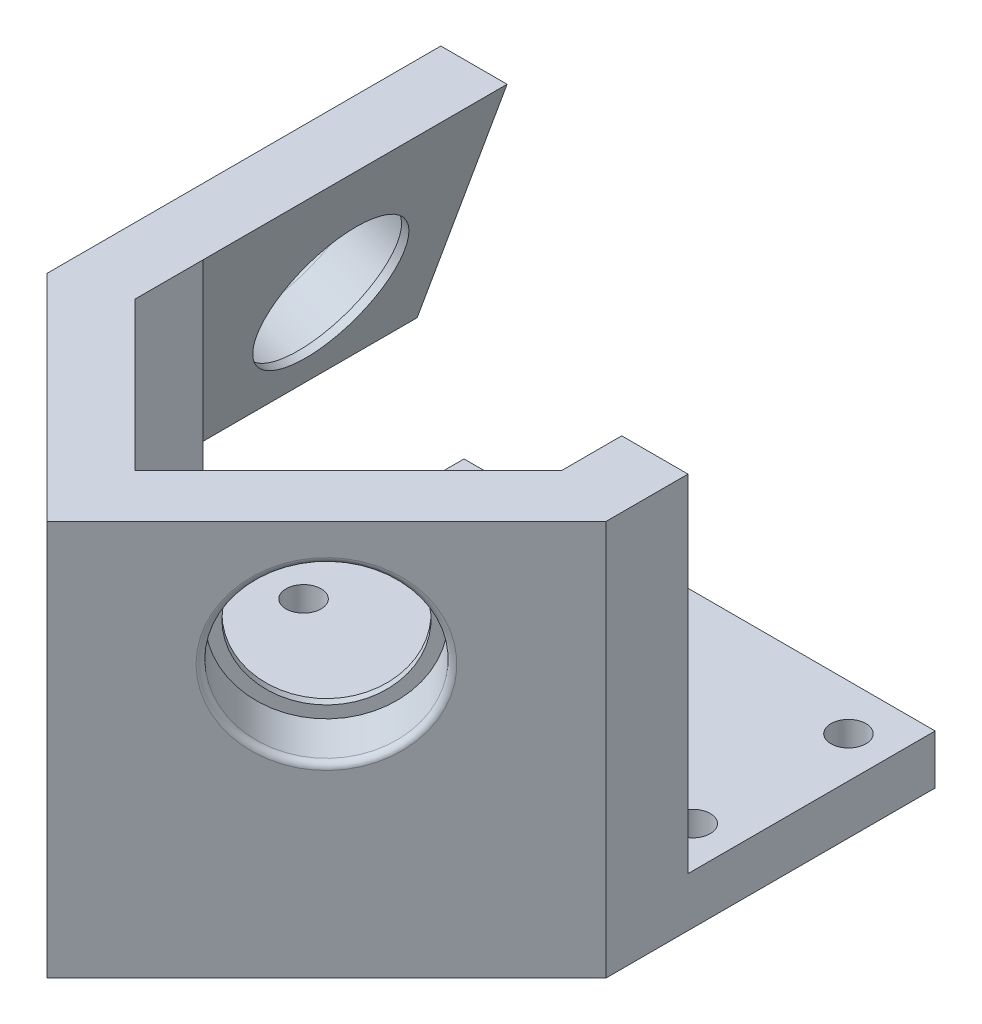
SolidWorks part; units mm, degrees
ref_plane "Front Plane" through (0, 0, 0) normal (0, 0, 1) x (1, 0, 0)
ref_plane "Top Plane" through (0, 0, 0) normal (0, 1, 0) x (1, 0, 0)
ref_plane "Right Plane" through (0, 0, 0) normal (1, 0, 0) x (0, 0, -1)
sketch "Sketch1" plane through (0, 0, 0) normal (0, 1, 0) x (1, 0, 0)
  line L0 (-35.921, 0) -> (0, 35.921)
  line L1 (-35.921, 0) -> (0, -35.921)
  line L2 (0, 35.921) -> (35.921, 0)
  line L3 (0, -35.921) -> (35.921, 0)
  line L4 (-35.921, 0) -> (35.921, 0) construction
  line L5 (0, 35.921) -> (0, -35.921) construction
  point P1 (0, 0)
  dimension "D1" = 50.8
  dimension "D2" = 50.8
extrude "Boss-Extrude1" add sketch "Sketch1" along normal mid plane 31.75
sketch "Sketch2" plane through (17.9605, 0, 17.9605) normal (0.7071, 0, 0.7071) x (0.7071, 0, -0.7071)
  circle A0 centre (0, 0) radius 11.05
  dimension "D1" = 22.1
extrude "Cut-Extrude1" cut sketch "Sketch2" against normal blind 8
sketch "Sketch3" plane through (-17.9605, 0, 17.9605) normal (-0.7071, 0, 0.7071) x (0.7071, 0, 0.7071)
  circle A0 centre (0, 0) radius 11.05
  dimension "D1" = 22.1
extrude "Cut-Extrude2" cut sketch "Sketch3" against normal blind 8
sketch "Sketch4" plane through (0, 15.875, 0) normal (0, 1, 0) x (1, 0, 0)
  line L0 (25.4, 10.521) -> (-25.4, 10.521)
  line L1 (35.921, 0) -> (0, 35.921) construction
  line L2 (0, 35.921) -> (-35.921, 0) construction
  line L3 (-25.4, 10.521) -> (0, 35.921)
  line L4 (0, 35.921) -> (25.4, 10.521)
  dimension "D1" = 25.4
extrude "Cut-Extrude3" cut sketch "Sketch4" against normal through all
sketch "Sketch5" plane through (0, 0, -10.521) normal (0, 0, -1) x (-1, 0, 0)
  line L0 (-35.921, 15.875) -> (-35.921, -15.875)
  line L1 (-35.921, -15.875) -> (39.135, -15.875)
  line L2 (39.135, -15.875) -> (27.579, 15.875)
  line L3 (27.579, 15.875) -> (-35.921, 15.875)
  line L4 (25.4, -15.875) -> (-25.4, -15.875) construction
  line L5 (-35.921, 15.875) -> (-35.921, -15.875) construction
  line L8 (25.4, 15.875) -> (-25.4, 15.875) construction
  point P6 (0, 0)
  dimension "D1" = 70
  dimension "D2" = 63.5
extrude "Boss-Extrude2" add sketch "Sketch5" against normal up to surface and the other way blind 31.75 up to face at (30.6605, 0, -5.2605)
sketch "Sketch6" plane through (-29.455, 10.7207, 0) normal (-0.9397, 0.342, 0) x (0, 0, 1)
  line L0 (-42.271, -28.3026) -> (-42.271, 5.4851) construction
  line L1 (-42.271, -28.3026) -> (-10.521, -28.3026) construction
  circle A0 centre (-26.396, -11.4088) radius 11.05
  point P4 (-42.271, -11.4088)
  point P7 (-26.396, -28.3026)
  dimension "D1" = 22.1
extrude "Cut-Extrude4" cut sketch "Sketch6" against normal through all
sketch "Sketch7" plane through (0, 0, -42.271) normal (0, 0, -1) x (-1, 0, 0)
  line L1 (-35.921, -15.875) -> (39.135, -15.875) construction
  line L3 (19.0656, 15.875) -> (30.6216, -15.875)
  line L4 (-35.921, -15.875) -> (30.6216, -15.875)
  line L5 (39.135, -15.875) -> (27.579, 15.875) construction
  line L6 (27.579, 15.875) -> (-35.921, 15.875) construction
  line L7 (-35.921, -15.875) -> (-35.921, 15.875)
  line L8 (-35.921, 15.875) -> (19.0656, 15.875)
  dimension "D3" = 8
extrude "Cut-Extrude5" cut sketch "Sketch7" against normal blind 31.75
sketch "Sketch8" plane through (0, 15.875, 0) normal (0, 1, 0) x (1, 0, 0)
  line L5 (-42.1413, -6.2203) -> (-8.2965, -39.8855)
  line L6 (0, -35.921) -> (0, -57.0039)
  line L13 (0, -57.0039) -> (-46.5861, -10.6651)
  line L14 (-46.5861, -10.6651) -> (-42.1413, -6.2203)
  line L15 (-8.2965, -39.8855) -> (-8.2965, -27.6245)
  line L16 (-35.921, 0) -> (0, -35.921) construction
  line L17 (-8.2965, -27.6245) -> (0, -35.921)
  line L18 (-25.4, 10.521) -> (-35.921, 0) construction
extrude "Boss-Extrude3" [suppressed] add sketch "Sketch8" against normal up to surface (25.4 mm away) up to face at (2.1042, -15.875, 2.9758)
sketch "Sketch9" plane through (0, -15.875, 0) normal (0, -1, 0) x (1, 0, 0)
  line L0 (-25.4, -10.521) -> (-35.921, 0)
  line L1 (-35.921, 0) -> (-46.442, -10.521)
  line L2 (-46.442, -10.521) -> (-25.4, -10.521)
  line L3 (-35.921, 0) -> (0, 35.921) construction
extrude "Boss-Extrude4" add sketch "Sketch9" against normal up to surface (31.75 mm away) up to face at (-9.1964, 15.875, -10.0783)
sketch "Sketch10" plane through (0, 0, -42.271) normal (0, 0, -1) x (-1, 0, 0)
  line L0 (39.135, -15.875) -> (27.579, 15.875) construction
  line L1 (39.135, -15.875) -> (27.579, 15.875)
  line L6 (27.579, 15.875) -> (39.135, -15.875)
  line L7 (39.135, -15.875) -> (46.442, -15.875)
  line L8 (46.442, -15.875) -> (46.442, 15.875)
  line L9 (46.442, 15.875) -> (27.579, 15.875)
  line L10 (27.579, 15.875) -> (39.135, -15.875)
  line L11 (39.135, -15.875) -> (46.442, -15.875)
  line L12 (46.442, -15.875) -> (46.442, 15.875)
  line L13 (46.442, 15.875) -> (27.579, 15.875)
  line M7 (39.135, -15.875) -> (27.579, 15.875)
  dimension "D1" = 0
extrude "Cut-Extrude6" cut sketch "Sketch10" against normal through all contours L12 L13 L11 M7 region at (-39.4743, 2.3367, -42.271)
sketch "Sketch11" plane through (0, -15.875, 0) normal (0, -1, 0) x (1, 0, 0)
  line L3 (-30.6216, -10.521) -> (-39.135, -10.521)
  line L4 (-39.135, -42.271) -> (-39.135, -3.214) construction
  line L5 (-39.135, -10.521) -> (-39.135, -3.214)
  line L10 (0, 35.921) -> (-39.135, -3.214)
  line L11 (-39.135, -3.214) -> (-39.135, -42.271)
  line L12 (-39.135, -42.271) -> (-30.6216, -42.271)
  line L13 (-30.6216, -42.271) -> (-30.6216, -10.521)
  line L21 (-30.6216, -10.521) -> (35.921, -10.521)
  line L22 (35.921, -10.521) -> (35.921, 0)
  line L23 (35.921, 0) -> (0, 35.921)
  line L24 (0, 35.921) -> (-39.135, -3.214)
  line L29 (-30.6216, -10.521) -> (35.921, -10.521)
  line L30 (35.921, -10.521) -> (35.921, 0)
  line L31 (35.921, 0) -> (0, 35.921)
  dimension "D1" = 0
extrude "Boss-Extrude5" add sketch "Sketch11" along normal blind 12.7
sketch "Sketch12" plane through (0, -28.575, 0) normal (0, -1, 0) x (1, 0, 0)
  line L0 (35.921, -10.521) -> (35.921, 0)
  line L1 (35.921, 0) -> (0, 35.921)
  line L2 (0, 35.921) -> (-39.135, -3.214)
  line L3 (-39.135, -3.214) -> (-39.135, -42.271)
  line L4 (-39.135, -42.271) -> (35.921, -42.271)
  line L5 (35.921, -42.271) -> (35.921, -10.521)
  point P10 (0, 0)
  point P13 (-36.8238, -0.9028)
extrude "Boss-Extrude6" add sketch "Sketch12" along normal blind 6.35
sketch "Sketch14" plane through (0, 0, -10.521) normal (0, 0, -1) x (-1, 0, 0)
  line L0 (35.244, -28.575) -> (19.0656, 15.875)
  line L1 (39.135, -34.925) -> (26.3581, -34.925)
  line L2 (19.0656, 15.875) -> (8.4238, 15.875)
  line L3 (24.6023, -28.575) -> (8.4238, 15.875)
  line L4 (19.0656, 15.875) -> (-35.921, 15.875) construction
  line L5 (30.6216, -15.875) -> (19.0656, 15.875) construction
  line L6 (39.135, -34.925) -> (-35.921, -34.925) construction
  line L7 (39.135, -34.925) -> (39.135, -28.575)
  line L8 (39.135, -28.575) -> (35.244, -28.575)
  line L9 (24.6023, -28.575) -> (24.6023, -34.925)
  line L10 (24.6023, -34.925) -> (26.3581, -34.925)
  line L11 (39.135, -28.575) -> (-35.921, -28.575) construction
  point P10 (23.5069, -23.9162)
  point P19 (39.135, -28.575)
  dimension "D1" = 10
extrude "Cut-Extrude7" cut sketch "Sketch14" along normal through all
sketch "Sketch15" plane through (0, -34.925, 0) normal (0, -1, 0) x (1, 0, 0)
  line L0 (-24.6023, -42.271) -> (35.921, -42.271) construction
  line L1 (30.6594, -16.396) -> (-19.3406, -16.396) construction
  line L2 (30.6594, -16.396) -> (30.6594, -36.396) construction
  line L3 (30.6594, -36.396) -> (-19.3406, -36.396) construction
  line L4 (-19.3406, -16.396) -> (-19.3406, -36.396) construction
  line L5 (30.6594, -16.396) -> (-19.3406, -36.396) construction
  line L6 (30.6594, -36.396) -> (-19.3406, -16.396) construction
  line L9 (-24.6023, -42.271) -> (-24.6023, -10.521) construction
  circle A0 centre (30.6594, -36.396) radius 2.25
  circle A1 centre (30.6594, -16.396) radius 2.25
  circle A2 centre (-19.3406, -16.396) radius 2.25
  circle A3 centre (-19.3406, -36.396) radius 2.25
  point P0 (5.6594, -26.396)
  point P11 (5.6594, -42.271)
  point P14 (-24.6023, -26.396)
  dimension "D1" = 4.5
  dimension "D2" = 50
  dimension "D3" = 20
extrude "Cut-Extrude8" cut sketch "Sketch15" against normal up to next
sketch "Sketch16" plane through (-21.9374, 7.9846, 0) normal (0.9397, -0.342, 0) x (0, 0, -1)
  circle A1 centre (26.396, -11.4088) radius 9.5
  circle A2 centre (26.396, -11.4088) radius 11.05 construction
  circle A3 centre (26.396, -11.4088) radius 11.05
  point P2 (0, 0)
  circle M8 centre (26.396, -11.4088) radius 11.05
  dimension "D1" = 19
extrude "Boss-Extrude7" add sketch "Sketch16" against normal offset from surface (1 mm away) 7 contours A1 M8 region at (-25.8395, -2.7362, -15.6586) up to face at (-37.1363, -10.3836, -26.396)
fillet "Fillet1" radius 0.7937 3 edges at (-37.1363, -10.3836, -26.396) (25.774, 0, 10.147) (-10.147, 0, 25.774)
sketch "Sketch17" plane through (0, 15.875, 0) normal (0, 1, 0) x (1, 0, 0)
  line L0 (-19.0656, 10.521) -> (-19.0656, -5.5418)
  line L1 (-19.0656, -5.5418) -> (0, -24.6073)
  line L2 (0, -24.6073) -> (27.4076, 2.8003)
  line L3 (27.4076, 2.8003) -> (27.4076, 10.521)
  line L4 (-19.0656, 10.521) -> (35.921, 10.521) construction
  line L5 (13.7038, -10.9035) -> (19.3607, -16.5604) construction
  line L6 (0, -35.921) -> (35.921, 0) construction
  line L7 (-9.5328, -15.0745) -> (-15.1896, -20.7314) construction
  line L8 (-27.579, -8.342) -> (0, -35.921) construction
  line L9 (27.4076, 10.521) -> (35.921, 10.521) construction
  line L10 (-19.0656, 10.521) -> (-27.579, 10.521) construction
  line L11 (-27.579, 42.271) -> (-27.579, -8.342) construction
  line L12 (-19.0656, 10.521) -> (27.4076, 10.521)
  dimension "D1" = 8
extrude "Cut-Extrude9" cut sketch "Sketch17" against normal up to surface (44.45 mm away) up to face at (-19.3406, -28.575, -34.146)
sketch "Sketch18" plane through (-12.3037, 0, 12.3037) normal (0.7071, 0, -0.7071) x (-0.7071, 0, -0.7071)
  circle A0 centre (0, 0) radius 9.5
  arc A1 (9.5628, 5.5368) -> (9.5628, -5.5368) centre (0, 0) ccw construction
  arc A2 (9.5628, 5.5368) -> (9.5628, -5.5368) centre (0, 0) ccw
  arc A3 (9.5628, 5.5368) -> (9.5628, -5.5368) centre (0, 0) cw
  dimension "D1" = 19
extrude "Boss-Extrude8" add sketch "Sketch18" against normal offset from surface (1 mm away) 7 up to face at (-26.3353, 0, 9.5857)
sketch "Sketch19" plane through (12.3037, 0, 12.3037) normal (-0.7071, 0, -0.7071) x (-0.7071, 0, 0.7071)
  circle A0 centre (0, 0) radius 9.5
  circle A1 centre (0, 0) radius 11.05 construction
  circle A2 centre (0, 0) radius 11.05
  dimension "D1" = 19
extrude "Boss-Extrude9" add sketch "Sketch19" against normal offset from surface (1 mm away) 7 up to face at (9.5857, 0, 26.3353)
sketch "Sketch20" plane through (0, 0, -10.521) normal (0, 0, -1) x (-1, 0, 0)
  line L7 (30.6216, -15.875) -> (19.0656, 15.875)
  line L8 (19.0656, 15.875) -> (19.0656, -28.575)
  line L9 (19.0656, -28.575) -> (24.6023, -28.575)
  line L10 (24.6023, -28.575) -> (24.6023, -34.925)
  line L11 (24.6023, -34.925) -> (39.135, -34.925)
  line L12 (39.135, -34.925) -> (39.135, -15.875)
  line L13 (39.135, -15.875) -> (30.6216, -15.875)
  line L14 (30.6216, -15.875) -> (19.0656, 15.875)
  line L15 (19.0656, 15.875) -> (19.0656, -28.575)
  line L16 (19.0656, -28.575) -> (24.6023, -28.575)
  line L17 (24.6023, -28.575) -> (24.6023, -34.925)
  line L18 (24.6023, -34.925) -> (39.135, -34.925)
  line L19 (39.135, -34.925) -> (39.135, -15.875)
  line L20 (39.135, -15.875) -> (30.6216, -15.875)
  dimension "D1" = 0
extrude "Cut-Extrude10" cut sketch "Sketch20" against normal up to vertex (7.307 mm away) up to point (-39.135, -34.925, -3.214)
